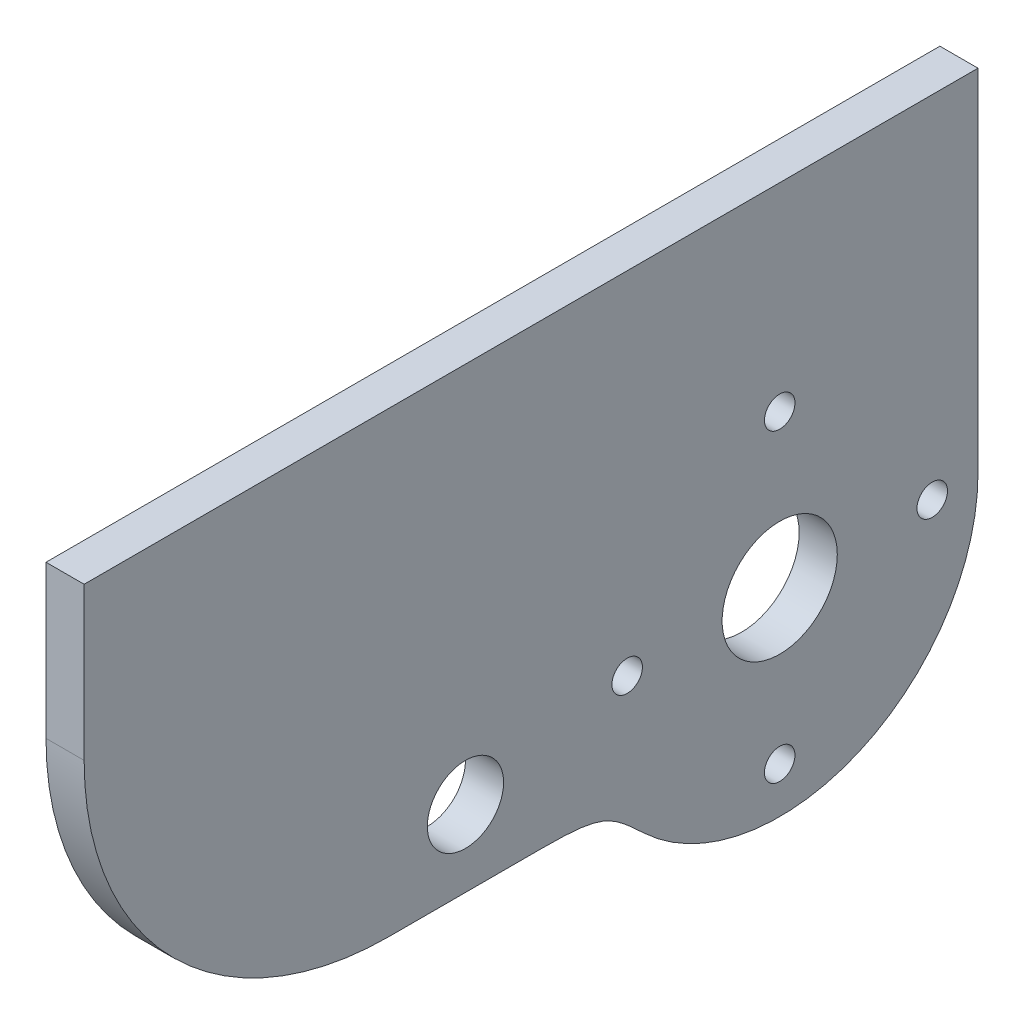
SolidWorks part; units mm, degrees
ref_plane "Front Plane" through (0, 0, 0) normal (0, 0, 1) x (1, 0, 0)
ref_plane "Top Plane" through (0, 0, 0) normal (0, 1, 0) x (1, 0, 0)
ref_plane "Right Plane" through (0, 0, 0) normal (1, 0, 0) x (0, 0, -1)
sketch "Sketch1" plane through (0, 0, 0) normal (1, 0, 0) x (0, 0, -1)
  line L0 (0, 0) -> (148.852, 0)
  line L1 (148.852, 0) -> (148.852, -58.42)
  line L2 (0, 0) -> (0, -25.4)
  line L3 (93.8063, -83.0319) -> (84.4724, -74.2914) construction
  line L4 (50.8, -76.2) -> (76.2, -76.2)
  line L5 (115.832, -58.42) -> (115.832, -33.02) construction
  line L6 (82.2061, -76.2) -> (69.8886, -76.2) construction
  arc A0 (148.852, -58.42) -> (93.2622, -82.5224) centre (115.832, -58.42) cw
  arc A1 (0, -25.4) -> (50.8, -76.2) centre (50.8, -25.4) ccw
  circle A2 centre (63.5, -63.5) radius 6.35
  circle A3 centre (115.832, -33.02) radius 2.54
  circle A4 centre (141.232, -58.42) radius 2.54
  circle A5 centre (115.832, -83.82) radius 2.54
  circle A6 centre (115.832, -58.42) radius 9.5885
  circle A7 centre (90.432, -58.42) radius 2.54
  spline S0 degree 3 poles (76.2, -76.2) (86.4095, -76.2) (87.6775, -77.2927) (93.2622, -82.5224) knots 0 0 0 0 1 1 1 1
  point P11 (63.5, -76.2)
  dimension "D4" = 52.578
  dimension "D6" = 12.7
  dimension "D8" = 33.02
  dimension "D9" = 19.177
  dimension "D11" = 5.08
  dimension "D12" = 25.4
  dimension "D1" = 25.4
  dimension "D2" = 25.4
  dimension "D3" = 76.2
  dimension "D5" = 12.7
  dimension "D7" = 63.5
  dimension "D10" = 58.42
  dimension "D13" = 4
extrude "Boss-Extrude1" add sketch "Sketch1" along normal blind 6.35
